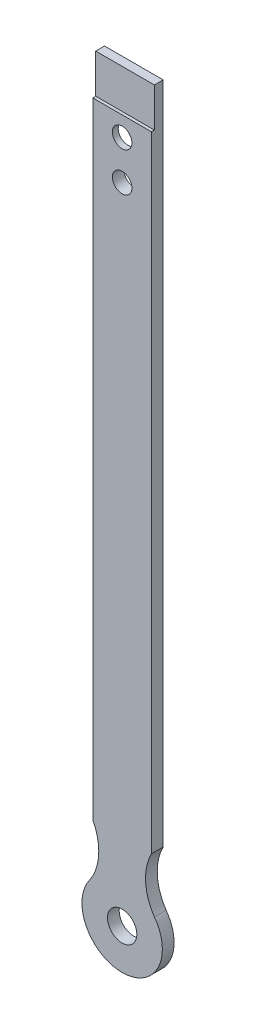
SolidWorks part; units mm, degrees
ref_plane "Спереди" through (0, 0, 0) normal (0, 0, 1) x (1, 0, 0)
ref_plane "Сверху" through (0, 0, 0) normal (0, 1, 0) x (1, 0, 0)
ref_plane "Справа" through (0, 0, 0) normal (1, 0, 0) x (0, 0, -1)
sketch "Эскиз1" plane through (0, 0, 0) normal (0, 0, 1) x (1, 0, 0)
  line L0 (15, 60.1262) -> (15, 400)
  line L1 (15, 400) -> (-15, 400)
  line L2 (0, 481.0809) -> (0, -73.6647) construction
  line L3 (-15, 60.1262) -> (-15, 400)
  arc A0 (-16.5121, 32.8596) -> (16.5121, 32.8596) centre (0, 20.5785) ccw
  arc A1 (16.5121, 32.8596) -> (15, 60.1262) centre (38.5826, 47.7588) cw
  arc A2 (-16.5121, 32.8596) -> (-15, 60.1262) centre (-38.5826, 47.7588) ccw
  circle A3 centre (0, 370) radius 5
  circle A4 centre (0, 350) radius 5
  circle A5 centre (0, 20.5785) radius 7.5
  point P13 (0, 400)
  point P15 (0, 0)
extrude "Бобышка-Вытянуть1" add sketch "Эскиз1" along normal blind 6
sketch "Эскиз2" plane through (-15, 0, 0) normal (-1, 0, 0) x (0, 0, 1)
  line L0 (4.5, 400) -> (4.5, 380)
  line L1 (6, 400) -> (0, 400) construction
  line L2 (4.5, 380) -> (6, 380)
  line L3 (6, 400) -> (6, 60.1262) construction
  line L4 (6, 380) -> (6, 400)
  line L5 (6, 400) -> (4.5, 400)
extrude "Вырез-Вытянуть1" cut sketch "Эскиз2" against normal through all
chamfer "Фаска1" distance 3 angle 60 1 edges at (5, 370, 0) first distance on face at (5, 370, 6)
